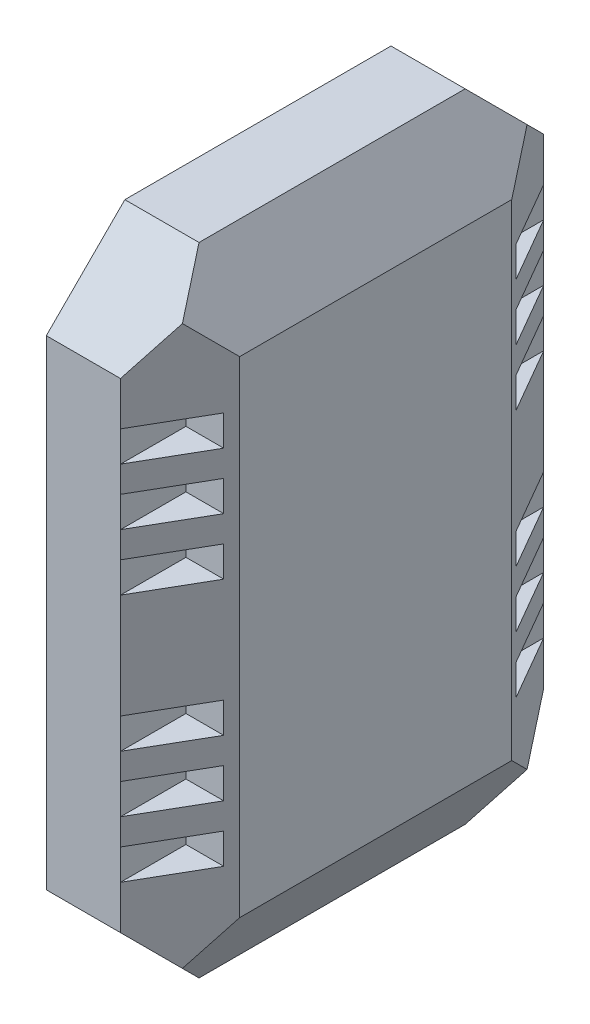
SolidWorks part; units mm, degrees
material "6061 Alloy"
ref_plane "Front Plane" through (0, 0, 0) normal (1, 0, 0) x (0, 1, 0)
ref_plane "Top Plane" through (0, 0, 0) normal (0, 0, 1) x (0, 1, 0)
ref_plane "Right Plane" through (0, 0, 0) normal (0, 1, 0) x (-1, 0, 0)
sketch "Sketch1" plane through (0, 0, 0) normal (1, 0, 0) x (0, 1, 0)
  line L0 (0, 0) -> (37.084, 0)
  line L1 (37.084, 0) -> (37.084, -24.638)
  line L2 (37.084, -24.638) -> (0, -24.638)
  line L3 (0, -24.638) -> (0, 0)
  dimension "D1" = 24.638
  dimension "D2" = 37.084
extrude "Boss-Extrude1" add sketch "Sketch1" along normal blind 6.858
chamfer "Chamfer2" distance 4.572 angle 45 4 edges at (3.429, 0, 0) (3.429, 0, -24.638) (3.429, 37.084, 0) (3.429, 37.084, -24.638)
chamfer "Chamfer3" distance 2.54 angle 60 2 edges at (6.858, 18.542, 0) (6.858, 18.542, -24.638) first distance on face at (3.429, 18.542, 0) first distance on face at (3.429, 18.542, -24.638)
chamfer "Chamfer4" distance 2.54 angle 60 2 edges at (6.858, 0, -12.319) (6.858, 37.084, -12.319) first distance on face at (3.429, 0, -12.319) first distance on face at (3.429, 37.084, -12.319)
sketch "Sketch3" plane through (0, 0, 0) normal (-1, 0, 0) x (0, -1, 0)
  line L0 (-32.512, 0) -> (-4.572, 0) construction
  line L1 (-28.542, -22.319) -> (-8.542, -22.319) construction
  line L2 (-28.542, -22.319) -> (-28.542, -2.319) construction
  line L3 (-28.542, -2.319) -> (-8.542, -2.319) construction
  line L4 (-8.542, -22.319) -> (-8.542, -2.319) construction
  line L5 (-28.542, -22.319) -> (-8.542, -2.319) construction
  line L6 (-28.542, -2.319) -> (-8.542, -22.319) construction
  line L7 (-37.084, -20.066) -> (-37.084, -4.572) construction
  circle A0 centre (-8.542, -2.319) radius 1
  circle A1 centre (-8.542, -22.319) radius 1
  circle A2 centre (-28.542, -22.319) radius 1
  circle A3 centre (-28.542, -2.319) radius 1
  point P0 (-18.542, -12.319)
  point P8 (-18.542, 0)
  point P11 (-37.084, -12.319)
  point P21 (-18.542, -12.319)
  dimension "D2" = 2
  dimension "D1" = 20
  dimension "D3" = 4
extrude "Cut-Extrude1" cut sketch "Sketch3" against normal blind 2.54 and the other way through all
sketch "Sketch4" plane through (6.858, 0, 0) normal (1, 0, 0) x (0, 1, 0)
  line L0 (4.572, 0) -> (32.512, 0) construction
  line L1 (7.112, 0) -> (8.89, 0)
  line L2 (7.112, 0) -> (7.112, -3.81)
  line L3 (7.112, -3.81) -> (8.89, -3.81)
  line L4 (8.89, 0) -> (8.89, -3.81)
  line L5 (18.542, 0) -> (18.542, -24.638) construction
  line L6 (10.414, 0) -> (12.192, 0)
  line L7 (10.414, 0) -> (10.414, -3.81)
  line L8 (10.414, -3.81) -> (12.192, -3.81)
  line L9 (12.192, 0) -> (12.192, -3.81)
  line L10 (13.716, 0) -> (15.494, 0)
  line L11 (13.716, 0) -> (13.716, -3.81)
  line L12 (13.716, -3.81) -> (15.494, -3.81)
  line L13 (15.494, 0) -> (15.494, -3.81)
  line L14 (32.512, -24.638) -> (4.572, -24.638) construction
  line L15 (0, -12.319) -> (37.084, -12.319) construction
  line L16 (0, -20.066) -> (0, -4.572) construction
  line L17 (37.084, -4.572) -> (37.084, -20.066) construction
  line L18 (21.59, 0) -> (21.59, -3.81)
  line L19 (23.368, -3.81) -> (21.59, -3.81)
  line L20 (23.368, 0) -> (23.368, -3.81)
  line L21 (23.368, 0) -> (21.59, 0)
  line L22 (24.892, 0) -> (24.892, -3.81)
  line L23 (26.67, -3.81) -> (24.892, -3.81)
  line L24 (26.67, 0) -> (26.67, -3.81)
  line L25 (26.67, 0) -> (24.892, 0)
  line L26 (28.194, 0) -> (28.194, -3.81)
  line L27 (29.972, -3.81) -> (28.194, -3.81)
  line L28 (29.972, 0) -> (29.972, -3.81)
  line L29 (29.972, 0) -> (28.194, 0)
  line L30 (29.972, -24.638) -> (28.194, -24.638)
  line L31 (29.972, -24.638) -> (29.972, -20.828)
  line L32 (29.972, -20.828) -> (28.194, -20.828)
  line L33 (28.194, -24.638) -> (28.194, -20.828)
  line L34 (26.67, -24.638) -> (24.892, -24.638)
  line L35 (26.67, -24.638) -> (26.67, -20.828)
  line L36 (26.67, -20.828) -> (24.892, -20.828)
  line L37 (24.892, -24.638) -> (24.892, -20.828)
  line L38 (23.368, -24.638) -> (21.59, -24.638)
  line L39 (23.368, -24.638) -> (23.368, -20.828)
  line L40 (23.368, -20.828) -> (21.59, -20.828)
  line L41 (21.59, -24.638) -> (21.59, -20.828)
  line L42 (15.494, -24.638) -> (15.494, -20.828)
  line L43 (13.716, -20.828) -> (15.494, -20.828)
  line L44 (13.716, -24.638) -> (13.716, -20.828)
  line L45 (13.716, -24.638) -> (15.494, -24.638)
  line L46 (12.192, -24.638) -> (12.192, -20.828)
  line L47 (10.414, -20.828) -> (12.192, -20.828)
  line L48 (10.414, -24.638) -> (10.414, -20.828)
  line L49 (10.414, -24.638) -> (12.192, -24.638)
  line L50 (8.89, -24.638) -> (8.89, -20.828)
  line L51 (7.112, -20.828) -> (8.89, -20.828)
  line L52 (7.112, -24.638) -> (7.112, -20.828)
  line L53 (7.112, -24.638) -> (8.89, -24.638)
  dimension "D1" = 3.81
  dimension "D2" = 1.778
  dimension "D3" = 1.524
  dimension "D4" = 1.524
  dimension "D5" = 2.54
extrude "Cut-Extrude2" cut sketch "Sketch4" against normal blind 2.54
sketch "Sketch5" plane through (0, 0, 0) normal (0, -1, 0) x (1, 0, 0)
  line L0 (4.318, -4.572) -> (0, -4.572) construction
  line L1 (4.318, -20.066) -> (4.318, -4.572) construction
  circle A0 centre (2.159, -12.319) radius 1.5875
  point P2 (0, 0)
  point P5 (2.159, -4.572)
  point P8 (4.318, -12.319)
  dimension "D1" = 3.175
extrude "Cut-Extrude3" cut sketch "Sketch5" against normal blind 3.81
